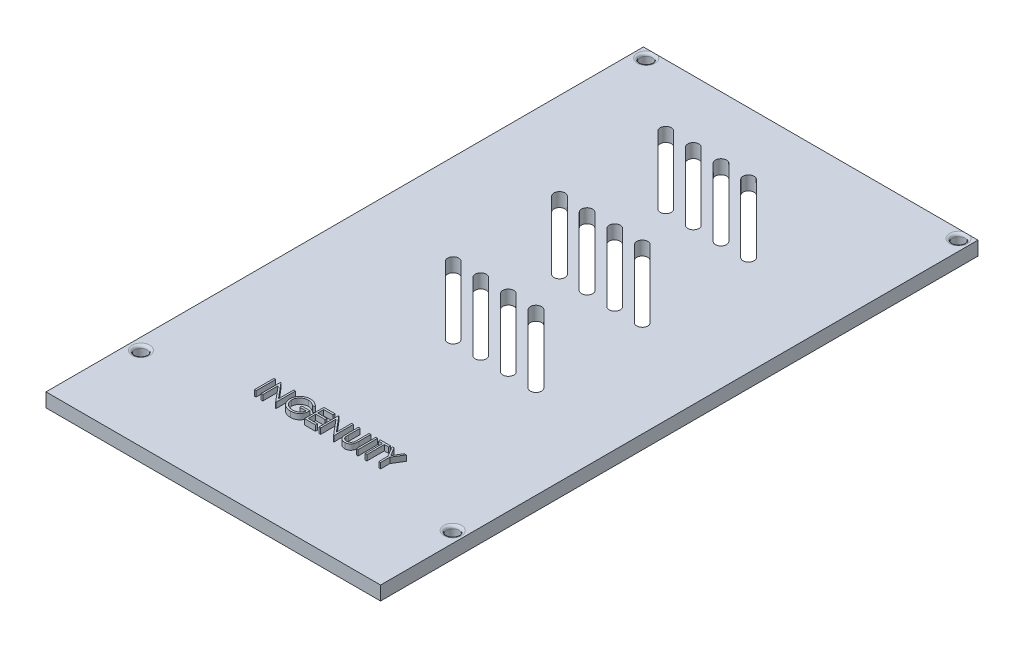
SolidWorks part; units mm, degrees
ref_plane "Front Plane" through (0, 0, 0) normal (0, 0, 1) x (1, 0, 0)
ref_plane "Top Plane" through (0, 0, 0) normal (0, 1, 0) x (1, 0, 0)
ref_plane "Right Plane" through (0, 0, 0) normal (1, 0, 0) x (0, 0, -1)
sketch "Sketch2" plane through (0, 0, 0) normal (0, 1, 0) x (1, 0, 0)
  line L1 (-30.1, 53.75) -> (30.1, 53.75)
  line L2 (-30.1, 53.75) -> (-30.1, -53.75)
  line L3 (-30.1, -53.75) -> (30.1, -53.75)
  line L4 (30.1, 53.75) -> (30.1, -53.75)
  line L5 (-30.1, 53.75) -> (30.1, -53.75) construction
  line L6 (-30.1, -53.75) -> (30.1, 53.75) construction
  circle A0 centre (-28.1, 52.25) radius 1.1
  circle A1 centre (28.1, 52.25) radius 1.1
  point P0 (0, 0)
  dimension "D1" = 107.5
  dimension "D2" = 60.2
extrude "Boss-Extrude2" add sketch "Sketch2" along normal blind 2.5
sketch3d "3DSketch2"
  circle A0 centre (-28.0414, 2.5, 38.7309) radius 1.1
  circle A1 centre (28.0991, 2.5, 38.7701) radius 1.1
  point P0 (28.0991, 2.5, 38.7701)
  point P6 (28.0991, 3.6, 38.7701)
  point P10 (-28.0414, 3.6, 38.7309)
extrude "Cut-Extrude4" cut sketch "3DSketch2" along direction (0, 1, 0) on the side of the normal through all from surface at 0
fillet "Fillet1" radius 0.5 4 edges at (28.1, 2.5, -53.35) (-28.1, 2.5, -51.15)
fillet "Fillet2" radius 0.5 1 edges
sketch "Sketch3" plane through (0, 2.5, 0) normal (0, 1, 0) x (1, 0, 0)
  line L0 (0, 42.5676) -> (12.1834, 30.3842) construction
  line L1 (0.7071, 43.2747) -> (12.8905, 31.0913)
  line L2 (-0.7071, 41.8605) -> (11.4763, 29.6771)
  line L3 (-4.9999, 42.6021) -> (7.1835, 30.4187) construction
  line L4 (-4.2928, 43.3092) -> (7.8906, 31.1258)
  line L5 (-5.707, 41.895) -> (6.4764, 29.7116)
  line L6 (-9.9998, 42.6366) -> (2.1836, 30.4532) construction
  line L7 (-9.2927, 43.3437) -> (2.8908, 31.1603)
  line L8 (-10.7069, 41.9295) -> (1.4765, 29.7461)
  line L9 (-14.9996, 42.6711) -> (-2.8162, 30.4877) construction
  line L10 (-14.2925, 43.3782) -> (-2.1091, 31.1948)
  line L11 (-15.7068, 41.964) -> (-3.5233, 29.7806)
  line L12 (-4.4083, 22.882) -> (7.7751, 10.6986) construction
  line L13 (-3.7012, 23.5891) -> (8.4822, 11.4057)
  line L14 (-5.1154, 22.1749) -> (7.068, 9.9915)
  line L15 (-9.4082, 22.9165) -> (2.7752, 10.7331) construction
  line L16 (-8.7011, 23.6236) -> (3.4824, 11.4402)
  line L17 (-10.1153, 22.2094) -> (2.0681, 10.026)
  line L18 (-14.408, 22.951) -> (-2.2246, 10.7676) construction
  line L19 (-13.7009, 23.6581) -> (-1.5175, 11.4747)
  line L20 (-15.1151, 22.2439) -> (-2.9317, 10.0604)
  line L21 (-3.8167, 3.1619) -> (8.3667, -9.0215) construction
  line L22 (-3.1096, 3.869) -> (9.0738, -8.3144)
  line L23 (-4.5238, 2.4548) -> (7.6596, -9.7286)
  line L24 (-8.8166, 3.1964) -> (3.3669, -8.9871) construction
  line L25 (-8.1094, 3.9035) -> (4.074, -8.2799)
  line L26 (-9.5237, 2.4892) -> (2.6597, -9.6942)
  line L27 (-13.8164, 3.2308) -> (-1.633, -8.9526) construction
  line L28 (-13.1093, 3.9379) -> (-0.9259, -8.2455)
  line L29 (-14.5235, 2.5237) -> (-2.3401, -9.6597)
  line L30 (0.5916, 22.8475) -> (12.775, 10.6641) construction
  line L31 (1.2987, 23.5546) -> (13.4821, 11.3712)
  line L32 (-0.1155, 22.1404) -> (12.0679, 9.957)
  line L33 (1.1832, 3.1274) -> (13.3666, -9.056) construction
  line L34 (1.8903, 3.8345) -> (14.0737, -8.3489)
  line L35 (0.4761, 2.4203) -> (12.6595, -9.7631)
  arc A0 (0.7071, 43.2747) -> (-0.7071, 41.8605) centre (0, 42.5676) ccw
  arc A1 (11.4763, 29.6771) -> (12.8905, 31.0913) centre (12.1834, 30.3842) ccw
  arc A2 (-4.2928, 43.3092) -> (-5.707, 41.895) centre (-4.9999, 42.6021) ccw
  arc A3 (6.4764, 29.7116) -> (7.8906, 31.1258) centre (7.1835, 30.4187) ccw
  arc A4 (-9.2927, 43.3437) -> (-10.7069, 41.9295) centre (-9.9998, 42.6366) ccw
  arc A5 (1.4765, 29.7461) -> (2.8908, 31.1603) centre (2.1836, 30.4532) ccw
  arc A6 (-14.2925, 43.3782) -> (-15.7068, 41.964) centre (-14.9996, 42.6711) ccw
  arc A7 (-3.5233, 29.7806) -> (-2.1091, 31.1948) centre (-2.8162, 30.4877) ccw
  arc A8 (-3.7012, 23.5891) -> (-5.1154, 22.1749) centre (-4.4083, 22.882) ccw
  arc A9 (7.068, 9.9915) -> (8.4822, 11.4057) centre (7.7751, 10.6986) ccw
  arc A10 (-8.7011, 23.6236) -> (-10.1153, 22.2094) centre (-9.4082, 22.9165) ccw
  arc A11 (2.0681, 10.026) -> (3.4824, 11.4402) centre (2.7752, 10.7331) ccw
  arc A12 (-13.7009, 23.6581) -> (-15.1151, 22.2439) centre (-14.408, 22.951) ccw
  arc A13 (-2.9317, 10.0604) -> (-1.5175, 11.4747) centre (-2.2246, 10.7676) ccw
  arc A14 (-3.1096, 3.869) -> (-4.5238, 2.4548) centre (-3.8167, 3.1619) ccw
  arc A15 (7.6596, -9.7286) -> (9.0738, -8.3144) centre (8.3667, -9.0215) ccw
  arc A16 (-8.1094, 3.9035) -> (-9.5237, 2.4892) centre (-8.8166, 3.1964) ccw
  arc A17 (2.6597, -9.6942) -> (4.074, -8.2799) centre (3.3669, -8.9871) ccw
  arc A18 (-13.1093, 3.9379) -> (-14.5235, 2.5237) centre (-13.8164, 3.2308) ccw
  arc A19 (-2.3401, -9.6597) -> (-0.9259, -8.2455) centre (-1.633, -8.9526) ccw
  arc A20 (1.2987, 23.5546) -> (-0.1155, 22.1404) centre (0.5916, 22.8475) ccw
  arc A21 (12.0679, 9.957) -> (13.4821, 11.3712) centre (12.775, 10.6641) ccw
  arc A22 (1.8903, 3.8345) -> (0.4761, 2.4203) centre (1.1832, 3.1274) ccw
  arc A23 (12.6595, -9.7631) -> (14.0737, -8.3489) centre (13.3666, -9.056) ccw
  point P2 (6.0917, 36.4759)
  point P11 (1.0918, 36.5104)
  point P18 (-3.9081, 36.5449)
  point P25 (-8.9079, 36.5794)
  point P32 (1.6834, 16.7903)
  point P39 (-3.3165, 16.8248)
  point P46 (-8.3163, 16.8593)
  point P53 (2.275, -2.9298)
  point P60 (-2.7249, -2.8954)
  point P67 (-7.7247, -2.8609)
  point P74 (6.6833, 16.7558)
  point P81 (7.2749, -2.9643)
  dimension "D1" = 4
  dimension "D2" = 3
extrude "Cut-Extrude5" cut sketch "Sketch3" against normal through all
sketch "Sketch4" plane through (0, 2.5, 0) normal (0, 1, 0) x (1, 0, 0)
  text T0 "INGENUITY"
extrude "Boss-Extrude3" add sketch "Sketch4" along normal blind 1
